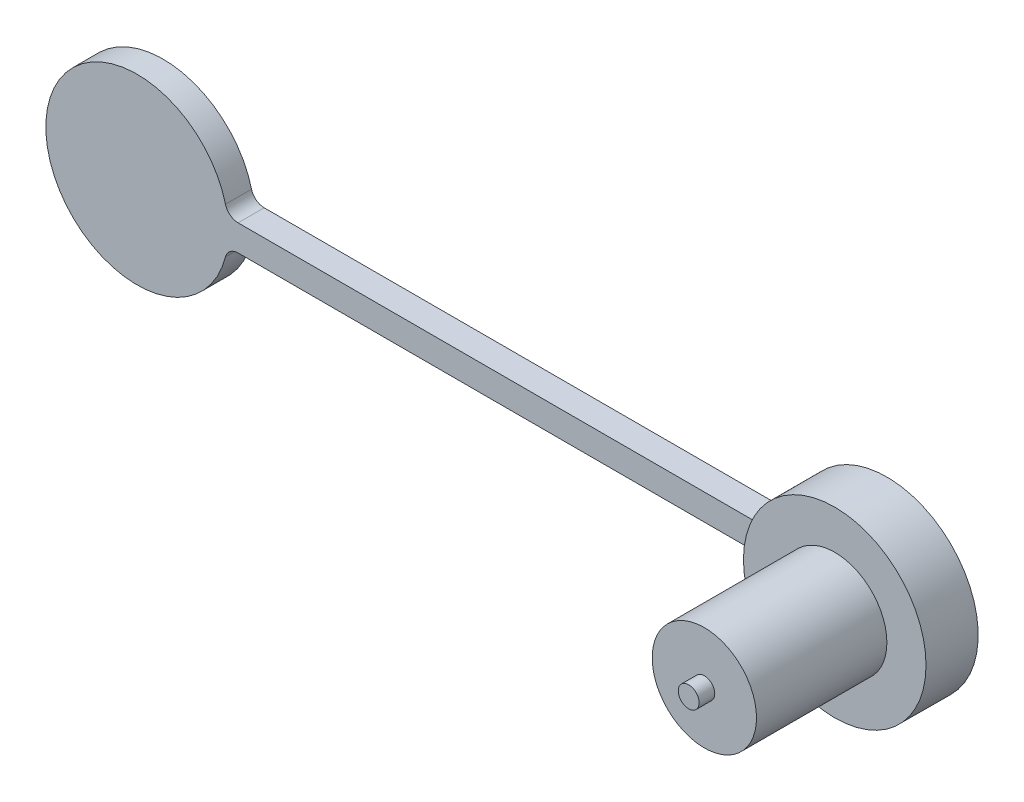
SolidWorks part; units mm, degrees
ref_plane "Plano frontal" through (0, 0, 0) normal (1, 0, 0) x (0, 1, 0)
ref_plane "Plano superior" through (0, 0, 0) normal (0, 0, 1) x (0, 1, 0)
ref_plane "Plano direito" through (0, 0, 0) normal (0, 1, 0) x (-1, 0, 0)
sketch "Esboço1" plane through (0, 0, 0) normal (0, 0, 1) x (0, 1, 0)
  circle A0 centre (0, 0) radius 35
extrude "Ressalto-extrusão1" add sketch "Esboço1" along normal blind 10
sketch "Esboço4" plane through (0, 0, 0) normal (1, 0, 0) x (0, 1, 0)
  line L0 (-35, 0) -> (35, 0) construction
  line L1 (-5, 10) -> (5, 10)
  line L2 (-5, 10) -> (-5, 0)
  line L3 (-5, 0) -> (5, 0)
  line L4 (5, 10) -> (5, 0)
  line L5 (-5, 10) -> (5, 0) construction
  line L6 (-5, 0) -> (5, 10) construction
  line L9 (35, 10) -> (-35, 10) construction
  point P0 (0, 5)
  dimension "D1" = 10
extrude "Ressalto-extrusão2" add sketch "Esboço4" along normal blind 277.5
fillet "Filete3" radius 5 1 edges at (34.641, -5, 5)
fillet "Filete4" radius 5 1 edges at (34.641, 5, 5)
sketch "Esboço6" plane through (0, 0, 10) normal (0, 0, 1) x (1, 0, 0)
  line L0 (277.5, 5) -> (277.5, -5) construction
  circle A0 centre (277.5, 0) radius 35
extrude "Ressalto-extrusão3" add sketch "Esboço6" against normal blind 10 and the other way blind 10
fillet "Filete5" radius 5 1 edges at (242.859, -5, 5)
fillet "Filete6" radius 5 1 edges at (242.859, 5, 5)
sketch "Esboço7" plane through (0, 0, 20) normal (0, 0, 1) x (1, 0, 0)
  circle A0 centre (277.5, 0) radius 20
extrude "Ressalto-extrusão4" add sketch "Esboço7" along normal blind 50
sketch3d "SMLINK_BETA_AXIS"
  line L0 (277.5, 0, 45) -> (277.5, 0, 95) construction
  point P0 (277.5, 0, 70)
ref_plane "SMLINK_BETA_PLANE" through (0, 0, 70) normal (0, 0, 1) x (0, 1, 0)
sketch "SMLINK_BETA_CIRCLE" plane through (0, 0, 70) normal (0, 0, 1) x (0, 1, 0)
  circle A0 centre (0, -277.5) radius 4
extrude "SMLINK_BETA_CYLINDER" add sketch "SMLINK_BETA_CIRCLE" along normal blind 6 separate body
